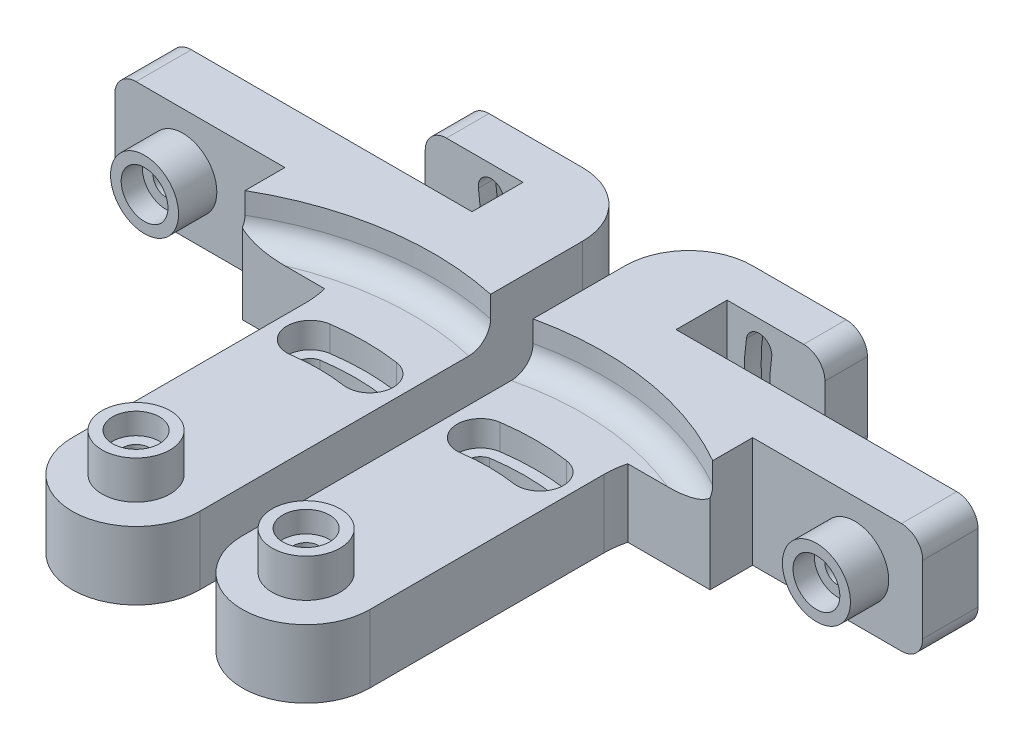
SolidWorks part; units mm, degrees
note: The reader was unsure of these and kept them because the rebuilt part matched: shared geometry of "Sketch6<8>".
ref_plane "Front Plane" through (0, 0, 0) normal (0, 0, 1) x (1, 0, 0)
ref_plane "Top Plane" through (0, 0, 0) normal (0, 1, 0) x (1, 0, 0)
ref_plane "Right Plane" through (0, 0, 0) normal (1, 0, 0) x (0, 0, -1)
sketch "Sketch1" plane through (0, 0, 0) normal (0, 1, 0) x (1, 0, 0)
  line L0 (0, 0) -> (0, 24.25) construction
  line L1 (0, -7.5) -> (0, 49000) construction
  line L2 (-7.5, 41.5) -> (-37.5, 41.5)
  line L3 (-37.5, 41.5) -> (-37.5, 37.5)
  line L5 (7.5, 0) -> (7.5, 45)
  line L6 (0, 52.5) -> (-13.5, 52.5)
  line L7 (-13.5, 52.5) -> (-13.5, 47.5)
  line L9 (-37.5, 37.5) -> (-17.5, 37.5)
  line L12 (-7.5, 0) -> (-7.5, 27.5)
  line L15 (-2, 47.5) -> (-2, 41.5)
  line L16 (-2, 41.5) -> (-7.5, 41.5)
  line L17 (-2, 47.5) -> (-13.5, 47.5)
  circle A1 centre (0, 0) radius 1.5
  arc A3 (3.5, 23.9961) -> (-3.5, 23.9961) centre (0, 0) ccw construction
  arc A4 (-3.8223, 25.4611) -> (-3.2806, 22.5122) centre (-3.5, 23.9961) ccw
  arc A5 (3.1835, 22.5262) -> (3.8663, 25.4544) centre (3.5, 23.9961) ccw
  arc A7 (3.8663, 25.4544) -> (-3.8223, 25.4611) centre (0, 0) ccw
  arc A8 (3.1835, 22.5262) -> (-3.2806, 22.5122) centre (0, 0) ccw
  arc A9 (7.5, 45) -> (0, 52.5) centre (0, 45) ccw
  arc A16 (-7.5, 0) -> (7.5, 0) centre (0, 0) ccw
  arc A17 (-7.5, 27.5) -> (-17.5, 37.5) centre (-17.5, 27.5) ccw
  dimension "D3" = 3
  dimension "D6" = 3
  dimension "D7" = 45
  dimension "D8" = 15
  dimension "D10" = 37.5
  dimension "D11" = 10
  dimension "D12" = 2
  dimension "D2" = 24.25
  dimension "D4" = 3.5
  dimension "D5" = 3.5
  dimension "D9" = 5
  dimension "D13" = 13.5
  dimension "D14" = 45
  dimension "D15" = 4
extrude "Boss-Extrude1" add sketch "Sketch1" along normal blind 8
sketch "Sketch2" plane through (0, 8, 0) normal (0, 1, 0) x (1, 0, 0)
  circle A0 centre (0, 0) radius 4
  circle A2 centre (0, 0) radius 1.5
  dimension "D1" = 8
  dimension "D2" = 3
extrude "Boss-Extrude2" add sketch "Sketch2" along normal blind 2
sketch "Sketch4" plane through (0, 10, 0) normal (0, 1, 0) x (1, 0, 0)
  circle A0 centre (0, 0) radius 4
  circle A1 centre (0, 0) radius 2.75
  dimension "D1" = 5.5
  dimension "D2" = 8
extrude "Boss-Extrude3" add sketch "Sketch4" along normal blind 2.5
sketch "Sketch5" plane through (0, 8, 0) normal (0, 1, 0) x (1, 0, 0)
  arc A0 (-3.8969, 26.7173) -> (-3.1031, 21.2749) centre (-3.5, 23.9961) ccw
  arc A1 (3.1031, 21.2749) -> (3.8969, 26.7173) centre (3.5, 23.9961) ccw
  arc A2 (3.8969, 26.7173) -> (-3.8969, 26.7173) centre (0, 0) ccw
  arc A3 (3.1031, 21.2749) -> (-3.1031, 21.2749) centre (0, 0) ccw
  dimension "D1" = 5.5
  dimension "D2" = 5.5
extrude "Cut-Extrude1" cut sketch "Sketch5" against normal blind 3
sketch "Sketch11" plane through (0, 8, 0) normal (0, 1, 0) x (1, 0, 0)
  line L0 (-2, 47.5) -> (-13.5, 47.5)
  line L3 (0, 52.5) -> (-13.5, 52.5)
  line L4 (-13.5, 52.5) -> (-13.5, 47.5)
  line L14 (-13.5, 47.5) -> (-2, 47.5)
  line L16 (-2, 41.5) -> (-37.5, 41.5)
  line L17 (-37.5, 41.5) -> (-37.5, 37.5)
  line L18 (-37.5, 37.5) -> (-17.5, 37.5)
  line L19 (-7.5, 27.5) -> (-7.5, 0)
  line L20 (7.5, 0) -> (7.5, 45)
  line L21 (0, 52.5) -> (-13.5, 52.5)
  line L27 (-2, 41.5) -> (-37.5, 41.5)
  line L28 (-37.5, 41.5) -> (-37.5, 37.5)
  line L29 (-37.5, 37.5) -> (-17.5, 37.5)
  line L30 (-7.5, 27.5) -> (-7.5, 0)
  line L31 (7.5, 0) -> (7.5, 45)
  line L34 (-13.5, 52.5) -> (-13.5, 47.5)
  line L37 (-2, 47.5) -> (-2, 41.5)
  line L38 (-2, 47.5) -> (-2, 41.5)
  arc A0 (7.5, 34.187) -> (-9.617, 33.6528) centre (0, 0) ccw
  arc A3 (-7.5, 27.5) -> (-17.5, 37.5) centre (-17.5, 27.5) ccw
  arc A4 (-7.5, 0) -> (7.5, 0) centre (0, 0) ccw
  arc A5 (7.5, 45) -> (0, 52.5) centre (0, 45) ccw
  arc A6 (-7.5, 27.5) -> (-17.5, 37.5) centre (-17.5, 27.5) ccw
  arc A7 (-7.5, 0) -> (7.5, 0) centre (0, 0) ccw
  arc A8 (7.5, 45) -> (0, 52.5) centre (0, 45) ccw
  dimension "D2" = 35
  dimension "D1" = 0
extrude "Boss-Extrude4" add sketch "Sketch11" along normal blind 5
sketch "Sketch12" plane through (0, 0, -37.5) normal (0, 0, 1) x (1, 0, 0)
  line L8 (-37.5, 0) -> (-17.5, 0)
  line L9 (-17.5, 0) -> (-17.5, 13)
  line L10 (-17.5, 13) -> (-37.5, 13)
  line L11 (-37.5, 13) -> (-37.5, 0)
  line L12 (-37.5, 0) -> (-17.5, 0)
  line L13 (-17.5, 0) -> (-17.5, 13)
  line L14 (-17.5, 13) -> (-37.5, 13)
  line L15 (-37.5, 13) -> (-37.5, 0)
  dimension "D1" = 0
extrude "Boss-Extrude5" add sketch "Sketch12" along normal blind 2.5
sketch "Sketch14" plane through (0, 0, 0) normal (0, 1, 0) x (1, 0, 0)
  line L0 (-17.5, 30.3109) -> (-17.5, 37.5)
  arc A0 (-9.617, 33.6528) -> (-17.5, 30.3109) centre (0, 0) ccw
  arc A1 (-9.617, 33.6528) -> (-17.5, 37.5) centre (-17.5, 27.5) ccw construction
  arc A2 (-9.617, 33.6528) -> (-17.5, 37.5) centre (-17.5, 27.5) ccw
extrude "Boss-Extrude6" add sketch "Sketch14" along normal up to surface (13 mm away) up to face at (-11.1377, 13, -42.2389)
sketch "Sketch15" plane through (0, 0, 0) normal (0, 1, 0) x (1, 0, 0)
  line L1 (-17.5, 30) -> (-17.5, 30.3109)
  line L2 (-17.5, 30) -> (-7.8175, 30)
  arc A0 (-7.5, 27.5) -> (-9.617, 33.6528) centre (-17.5, 27.5) ccw construction
  arc A1 (-7.8175, 30) -> (-9.617, 33.6528) centre (-17.5, 27.5) ccw
  arc A2 (7.5, 34.187) -> (-17.5, 30.3109) centre (0, 0) ccw construction
  arc A3 (-9.617, 33.6528) -> (-17.5, 30.3109) centre (0, 0) ccw
  point P8 (0, 0)
extrude "Boss-Extrude7" add sketch "Sketch15" along normal up to surface (8 mm away) up to face at (-1.8271, 8, -17.816)
sketch "Sketch6" plane through (0, 0, -52.5) normal (0, 0, -1) x (-1, 0, 0)
  line L0 (2, 0) -> (37.5, 0) construction
  line L1 (37.5, 13) -> (37.5, 0) construction
  line L2 (29.5, 6.5) -> (-18.8, 6.5) construction
  line L3 (29.5, -993.5) -> (29.5, 49006.5) construction
  circle A0 centre (29.5, 6.5) radius 1.5
  circle A1 centre (5.5, 6.5) radius 1.5 construction
  arc A3 (7.2405, 9.7812) -> (4.2726, 10.2188) centre (5.7566, 10) ccw
  arc A4 (4.2726, 2.7812) -> (7.2405, 3.2187) centre (5.7566, 3) ccw
  arc A8 (7.2405, 9.7812) -> (7.2405, 3.2187) centre (29.5, 6.5) ccw
  arc A9 (4.2726, 10.2188) -> (4.2726, 2.7812) centre (29.5, 6.5) ccw
  arc A14 (8.4772, 9.599) -> (3.036, 10.401) centre (5.7566, 10) ccw
  arc A18 (3.036, 10.401) -> (3.036, 2.599) centre (29.5, 6.5) ccw
  arc A19 (8.4772, 9.599) -> (8.4772, 3.401) centre (29.5, 6.5) ccw
  arc A20 (3.036, 2.599) -> (8.4772, 3.401) centre (5.7566, 3) ccw
  dimension "D1" = 3
  dimension "D4" = 3
  dimension "D8" = 3
  dimension "D9" = 3
  dimension "D10" = 25.5
  dimension "D11" = 5.5
  dimension "D12" = 22.5
  dimension "D13" = 2.75
  dimension "D2" = 6.5
  dimension "D3" = 24
  dimension "D5" = 8
  dimension "D6" = 3.5
  dimension "D7" = 3.5
extrude "Cut-Extrude5" cut sketch "Sketch6" against normal blind 17 contours A3 A9 A4 A8 | A0
extrude "Cut-Extrude6" cut sketch "Sketch6<8>" against normal blind 3
sketch "Sketch6<8>" plane through (0, 0, -52.5) normal (0, 0, -1) x (-1, 0, 0) same geometry as "Sketch6"
sketch "Sketch17" plane through (0, 0, -35) normal (0, 0, 1) x (1, 0, 0)
  circle A0 centre (-29.5, 6.5) radius 4
  circle A1 centre (-29.5, 6.5) radius 1.5
  dimension "D1" = 8
  dimension "D2" = 3
extrude "Boss-Extrude8" add sketch "Sketch17" along normal blind 2
sketch "Sketch18" plane through (0, 0, -33) normal (0, 0, 1) x (1, 0, 0)
  circle A0 centre (-29.5, 6.5) radius 4
  circle A1 centre (-29.5, 6.5) radius 2.75
  dimension "D1" = 5.5
  dimension "D2" = 8
extrude "Boss-Extrude9" add sketch "Sketch18" along normal blind 2.5
fillet "Fillet3" radius 2.5 5 edges at (-13.5, 0, -50) (-13.5, 13, -50) (-37.5, 0, -38.25) (-37.5, 13, -38.25) (-5.3625, 8, -34.5868)
ref_plane "Plane1" through (10, 0, 0) normal (1, 0, 0) x (0, 0, -1)
sketch "Sketch21" plane through (0, 0, -35) normal (0, 0, 1) x (1, 0, 0)
  circle A1 centre (-29.5, 6.5) radius 1.5
  circle A2 centre (-29.5, 6.5) radius 1.5
  dimension "D1" = 0
extrude "Cut-Extrude7" cut sketch "Sketch21" against normal blind 10
mirror "Mirror4" about plane through (10, 0, 0) normal (1, 0, 0) of bodies 124
